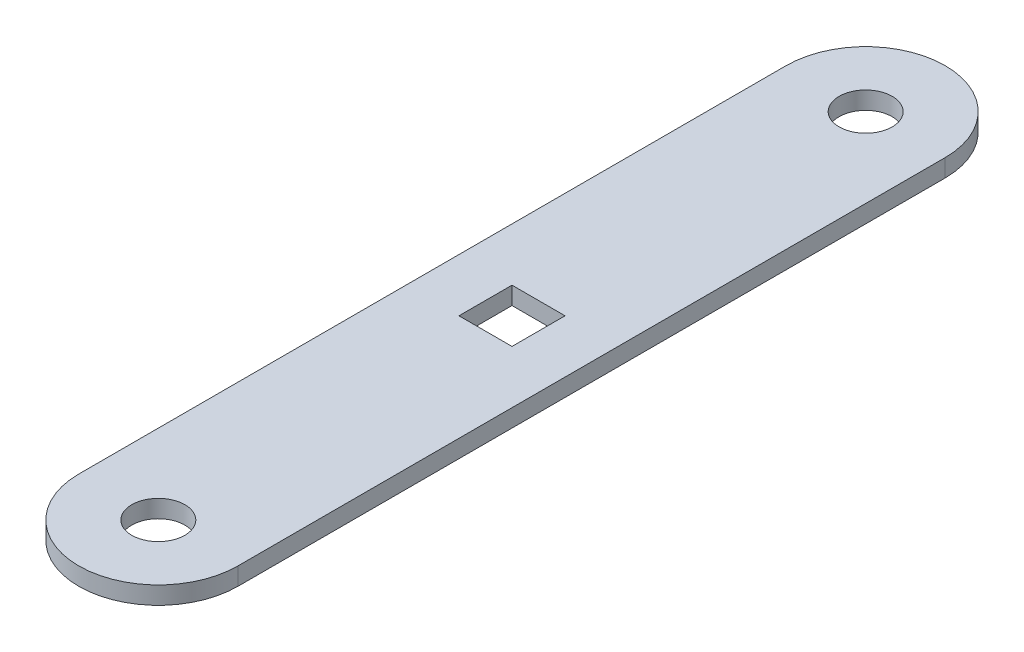
SolidWorks part; units mm, degrees
ref_plane "Front Plane" through (0, 0, 0) normal (0, 0, 1) x (1, 0, 0)
ref_plane "Top Plane" through (0, 0, 0) normal (0, 1, 0) x (1, 0, 0)
ref_plane "Right Plane" through (0, 0, 0) normal (1, 0, 0) x (0, 0, -1)
sketch "Sketch1" plane through (0, 0, 0) normal (0, 1, 0) x (1, 0, 0)
  line L1 (-225, -1000) -> (225, -1000)
  line L2 (-225, -1000) -> (-225, 1000)
  line L3 (-225, 1000) -> (225, 1000)
  line L4 (225, -1000) -> (225, 1000)
  line L5 (-225, -1000) -> (225, 1000) construction
  line L6 (-225, 1000) -> (225, -1000) construction
  arc A0 (225, -1000) -> (-225, -1000) centre (0, -1000) cw
  arc A1 (225, 1000) -> (-225, 1000) centre (0, 1000) ccw
  point P0 (0, 0)
  dimension "D1" = 2000
  dimension "D2" = 450
extrude "Boss-Extrude1" add sketch "Sketch1" along normal blind 50 contours L1 L4 L3 L2 | L3 A1 | A0 L1 region at (0, 0, 0) region at (0, 0, 1095.493) region at (0, 0, -1095.493)
sketch "Sketch2" plane through (0, 50, 0) normal (0, 1, 0) x (1, 0, 0)
  line L0 (-225, -1000) -> (225, -1000)
  line L1 (-225, -1000) -> (-225, 1000) construction
  circle A0 centre (0, -1000) radius 75
sketch "Sketch3" plane through (0, 50, 0) normal (0, 1, 0) x (1, 0, 0)
  line L0 (-225, 1000) -> (225, 1000)
  circle A0 centre (0, 1000) radius 75
extrude "Cut-Extrude2" cut sketch "Sketch3" against normal blind 250 contours L0 A0 | L0 A0 region at (0, 50, -1031.831) region at (0, 50, -968.169)
extrude "Cut-Extrude4" cut sketch "Sketch2" against normal through all contours L0 A0 | L0 A0 region at (0, 50, 968.169) region at (0, 50, 1031.831)
sketch "Sketch4" plane through (0, 50, 0) normal (0, 1, 0) x (1, 0, 0)
  line L1 (-75, -75) -> (75, -75)
  line L2 (-75, -75) -> (-75, 75)
  line L3 (-75, 75) -> (75, 75)
  line L4 (75, -75) -> (75, 75)
  line L5 (-75, -75) -> (75, 75) construction
  line L6 (-75, 75) -> (75, -75) construction
  point P0 (0, 0)
  dimension "D1" = 150
  dimension "D2" = 150
extrude "Cut-Extrude5" cut sketch "Sketch4" against normal through all
